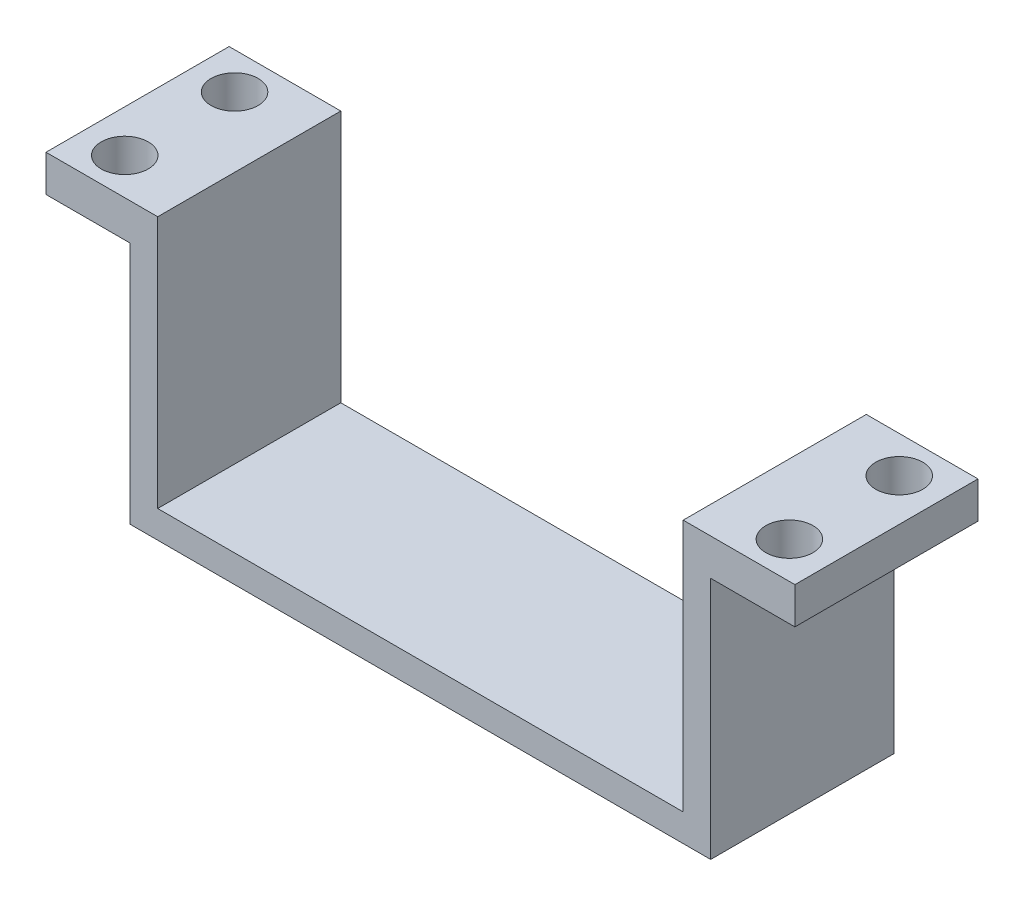
SolidWorks part; units mm, degrees
ref_plane "Front Plane" through (0, 0, 0) normal (0, 0, 1) x (1, 0, 0)
ref_plane "Top Plane" through (0, 0, 0) normal (0, 1, 0) x (1, 0, 0)
ref_plane "Right Plane" through (0, 0, 0) normal (1, 0, 0) x (0, 0, -1)
sketch "Sketch1" plane through (0, 0, 0) normal (0, 0, 1) x (1, 0, 0)
  line L0 (0, 0) -> (0, -35.052)
  line L1 (0, -35.052) -> (72.898, -35.052)
  line L2 (72.898, -35.052) -> (72.898, 0)
  line L3 (72.898, 0) -> (76.708, 0)
  line L4 (76.708, 0) -> (76.708, -38.862)
  line L5 (76.708, -38.862) -> (-3.81, -38.862)
  line L6 (-3.81, -38.862) -> (-3.81, 0)
  line L7 (-3.81, 0) -> (0, 0)
  dimension "D1" = 35.052
  dimension "D2" = 72.898
  dimension "D3" = 3.81
  dimension "D4" = 3.81
extrude "Boss-Extrude1" add sketch "Sketch1" along normal blind 25.4
sketch "Sketch2" plane through (0, 0, 0) normal (0, 1, 0) x (1, 0, 0)
  line L0 (0, 0) -> (-15.494, 0)
  line L1 (0, 0) -> (0, -25.4)
  line L2 (0, -25.4) -> (-15.494, -25.4)
  line L3 (-15.494, 0) -> (-15.494, -25.4)
  line L4 (-9.652, -5.08) -> (-9.652, -20.32) construction
  line L5 (0, -25.4) -> (0, 0) construction
  line L6 (-3.81, -25.4) -> (-3.81, 0) construction
  line L7 (0, 0) -> (-3.81, 0) construction
  line L8 (0, -25.4) -> (-3.81, -25.4) construction
  circle A0 centre (-9.652, -5.08) radius 3.2639
  circle A1 centre (-9.652, -20.32) radius 3.2639
  point P8 (-15.494, -12.7)
  point P9 (-9.652, -12.7)
  dimension "D1" = 6.5278
  dimension "D2" = 7.62
  dimension "D3" = 5.842
  dimension "D4" = 5.842
extrude "Boss-Extrude2" add sketch "Sketch2" against normal blind 5.08
ref_plane "Plane1" through (36.449, 0, 0) normal (1, 0, 0) x (0, 0, -1)
mirror "Mirror1" about plane through (36.449, 0, 0) normal (1, 0, 0) of "Boss-Extrude2"
